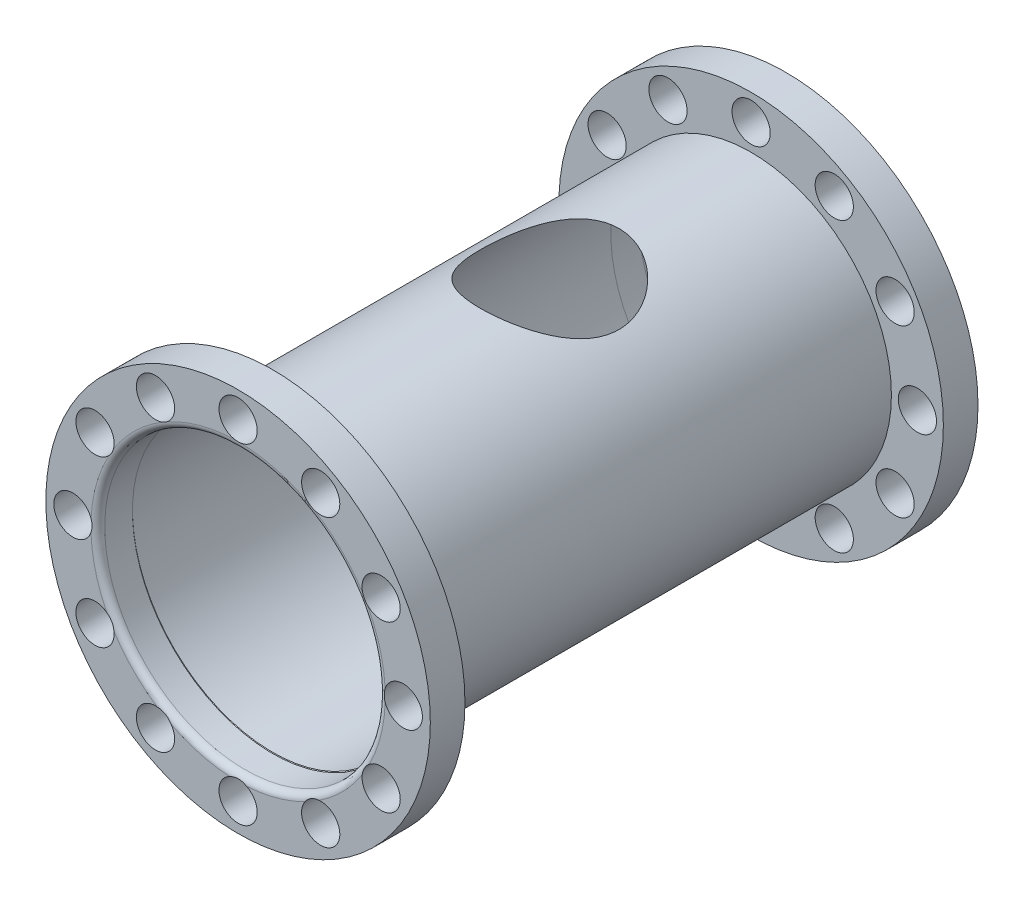
SolidWorks part; units mm, degrees
ref_plane "Front Plane" through (0, 0, 0) normal (0, 0, 1) x (1, 0, 0)
ref_plane "Top Plane" through (0, 0, 0) normal (0, 1, 0) x (1, 0, 0)
ref_plane "Right Plane" through (0, 0, 0) normal (1, 0, 0) x (0, 0, -1)
sketch "Sketch1" plane through (0, 0, 0) normal (0, 0, 1) x (1, 0, 0)
  line L0 (0, 55.5061) -> (0, 40.5061) construction
  circle A0 centre (0, 0) radius 55.5061
  circle A1 centre (0, 0) radius 40.5061
  circle A2 centre (0, 48.0061) radius 5.5187
  circle A3 centre (24.0031, 41.5745) radius 5.5187
  circle A4 centre (41.5745, 24.0031) radius 5.5187
  circle A5 centre (48.0061, 0) radius 5.5187
  circle A6 centre (41.5745, -24.0031) radius 5.5187
  circle A7 centre (24.0031, -41.5745) radius 5.5187
  circle A8 centre (0, -48.0061) radius 5.5187
  circle A9 centre (-24.0031, -41.5745) radius 5.5187
  circle A10 centre (-41.5745, -24.0031) radius 5.5187
  circle A11 centre (-48.0061, 0) radius 5.5187
  circle A12 centre (-41.5745, 24.0031) radius 5.5187
  circle A13 centre (-24.0031, 41.5745) radius 5.5187
  point P33 (0, 0)
  dimension "D2" = 11.0374
  dimension "D3" = 111.0122
  dimension "D1" = 15
  dimension "D4" = 12
sketch "Sketch4" plane through (0, 0, 0) normal (1, 0, 0) x (0, 0, -1)
  line L1 (16.8701, -38.1895) -> (-133.1299, -38.1895)
  line L2 (16.8701, -38.1895) -> (16.8701, 43.4772)
  line L3 (16.8701, 43.4772) -> (-133.1299, 43.4772)
  line L4 (-133.1299, -38.1895) -> (-133.1299, 43.4772)
  line L5 (16.8701, -38.1895) -> (-133.1299, 43.4772) construction
  line L6 (16.8701, 43.4772) -> (-133.1299, -38.1895) construction
  point P4 (-58.1299, 2.6439)
  point P5 (0, 0)
  dimension "D1" = 150
  dimension "D2" = 81.6667
ref_plane "Plane2" through (0, 0, 138.1299) normal (0, 0, 1) x (1, 0, 0)
sketch "Sketch5" plane through (0, 0, 138.1299) normal (0, 0, 1) x (1, 0, 0)
  line L0 (0, 55.1959) -> (0, 40.1959) construction
  circle A0 centre (0, -0.3102) radius 55.5061
  circle A1 centre (0, -0.3102) radius 40.5061
  circle A2 centre (0, 47.6959) radius 5.5187
  circle A3 centre (23.8479, 41.3059) radius 5.5187
  circle A4 centre (41.3059, 23.8479) radius 5.5187
  circle A5 centre (47.6959, 0) radius 5.5187
  circle A6 centre (41.3059, -23.8479) radius 5.5187
  circle A7 centre (23.8479, -41.3059) radius 5.5187
  circle A8 centre (0, -47.6959) radius 5.5187
  circle A9 centre (-23.8479, -41.3059) radius 5.5187
  circle A10 centre (-41.3059, -23.8479) radius 5.5187
  circle A11 centre (-47.6959, 0) radius 5.5187
  circle A12 centre (-41.3059, 23.8479) radius 5.5187
  circle A13 centre (-23.8479, 41.3059) radius 5.5187
  point P30 (0, -0.3102)
  point P34 (0, 0)
  dimension "D1" = 11.0374
  dimension "D2" = 111.0122
  dimension "D3" = 81.0122
  dimension "D4" = 47.6959
  dimension "D5" = 12
extrude "Boss-Extrude1" add sketch "Sketch5" along normal blind 10
extrude "Boss-Extrude2" add sketch "Sketch1" against normal blind 10 separate body
fillet "Fillet1" radius 2 1 edges at (40.5061, -0.3102, 148.1299)
surface "Surface-Extrude1" sketch "Sketch1<4>"
sketch "Sketch1<4>" plane through (0, 0, 0) normal (0, 0, 1) x (1, 0, 0) same geometry as "Sketch1"
fillet "Fillet4" radius 2 1 edges at (40.5061, 0, -10)
ref_plane "Plane3" through (0, 47.6439, 0) normal (0, 1, 0) x (1, 0, 0)
sketch "Sketch7" plane through (0, 47.6439, 0) normal (0, 1, 0) x (1, 0, 0)
  circle A1 centre (0, -58.1299) radius 20
  point P2 (0, 0)
  dimension "D1" = 40
surface "Surface-Trim1"
